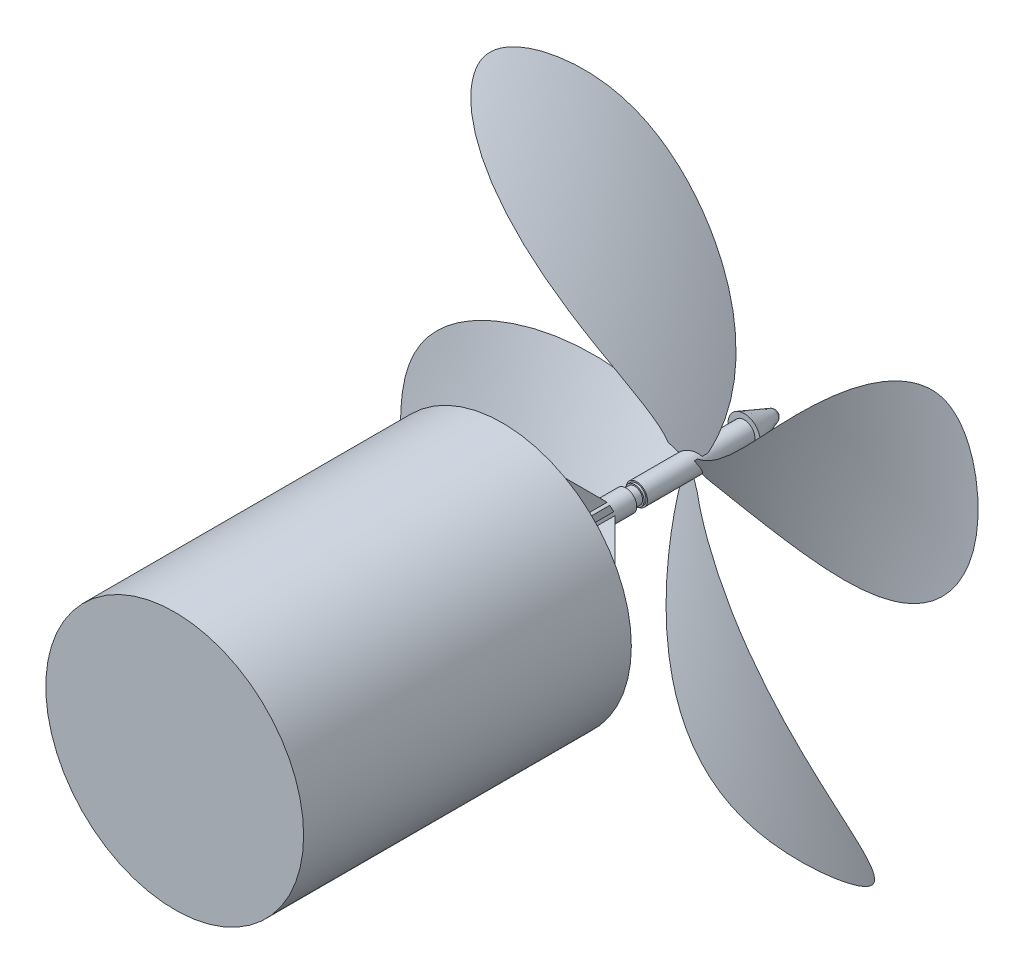
SolidWorks part; units mm, degrees
material "Gray Cast Iron"
ref_plane "Front Plane" through (0, 0, 0) normal (0, 0, 1) x (1, 0, 0)
ref_plane "Top Plane" through (0, 0, 0) normal (0, 1, 0) x (1, 0, 0)
ref_plane "Right Plane" through (0, 0, 0) normal (1, 0, 0) x (0, 0, -1)
sketch "Sketch1" plane through (0, 0, 0) normal (0, 0, 1) x (1, 0, 0)
  circle A0 centre (0, 0) radius 12
  dimension "D1" = 24
extrude "Boss-Extrude1" add sketch "Sketch1" along normal blind 30
sketch "Sketch3" plane through (0, 0, 0) normal (0, 0, 1) x (1, 0, 0)
  circle A0 centre (0, 0) radius 1
  dimension "D1" = 2
extrude "Boss-Extrude2" add sketch "Sketch3" against normal blind 15
sketch "Sketch4" plane through (0, 0, 0) normal (0, 0, 1) x (1, 0, 0)
  line L0 (0.5, 0) -> (0, 0) construction
  line L1 (0, 1) -> (0, -1) construction
  line L2 (0.5, 0) -> (0.5, 0.866) construction
  line L3 (0.25, 0) -> (0.25, 0.9682) construction
  line L4 (0.25, 0.9682) -> (0.25, 10.9682)
  line L5 (-0.25, 0.9682) -> (-0.25, 10.9682)
  line L6 (0.25, 10.9682) -> (-0.25, 10.9682)
  circle A0 centre (0, 0) radius 1 construction
  circle A1 centre (0, 0) radius 1 construction
  arc A2 (-0.25, 0.9682) -> (0.25, 0.9682) centre (0, 0) cw
  dimension "D1" = 10
extrude "Boss-Extrude3" add sketch "Sketch4" against normal blind 10 contours L5 A2 L4 L6
chamfer "Chamfer1" distance 10 angle 45 1 edges at (0, 10.9682, -10)
pattern_circular "CirPattern1" count 8 every 45 about axis through (0, 0, 0) along (0, 0, 1) of "Boss-Extrude3", "Chamfer1"
sketch "Sketch5" plane through (0, 0, 0) normal (0, 0, 1) x (1, 0, 0)
  circle A0 centre (0, 0) radius 12
  circle A1 centre (0, 0) radius 10.9682
extrude "Boss-Extrude4" add sketch "Sketch5" against normal blind 0.5
ref_plane "Plane1" through (0, 0, -12) normal (0, 0, 1) x (1, 0, 0)
sketch "Sketch6" plane through (0, 0, -12) normal (0, 0, 1) x (1, 0, 0)
  circle A0 centre (0, 0) radius 1
  circle A1 centre (0, 0) radius 0.75
  dimension "D1" = 1.5
extrude "Cut-Extrude1" cut sketch "Sketch6" against normal through all
ref_plane "Plane2" through (0, 0, -13) normal (0, 0, 1) x (1, 0, 0)
sketch "Sketch7" plane through (0, 0, -13) normal (0, 0, 1) x (1, 0, 0)
  line L0 (-0.75, 0) -> (-1, 0) construction
  circle A0 centre (0, 0) radius 0.75 construction
  arc A1 (-0.9682, 0.25) -> (-0.9682, -0.25) centre (0, 0) ccw construction
  circle A2 centre (0, 0) radius 0.875
  circle A3 centre (0, 0) radius 1 construction
  point P10 (0.875, 0)
  dimension "D1" = 0.125
extrude "Boss-Extrude5" add sketch "Sketch7" along normal blind 0.2
ref_plane "Plane3" through (0, 0, -15) normal (0, 0, 1) x (1, 0, 0)
sketch "Sketch8" plane through (0, 0, -15) normal (0, 0, 1) x (1, 0, 0)
  circle A0 centre (0, 0) radius 0.75
extrude "Boss-Extrude6" add sketch "Sketch8" against normal blind 8
ref_plane "Plane4" through (0, 0, -23) normal (0, 0, -1) x (-1, 0, 0)
sketch "Sketch9" plane through (0, 0, -23) normal (0, 0, -1) x (-1, 0, 0)
  circle A0 centre (0, 0) radius 1.5
  dimension "D1" = 3
sketch "Sketch10" plane through (0, 0, -23) normal (0, 0, -1) x (-1, 0, 0)
  circle A0 centre (0, 0) radius 1
  dimension "D1" = 2
ref_plane "Plane5" through (0, 28, 0) normal (0, 1, 0) x (1, 0, 0)
extrude "Boss-Extrude9" add sketch "Sketch10" against normal blind 10
extrude "Boss-Extrude10" add sketch "Sketch9" along normal blind 3 draft 20
fillet "Fillet2" radius 0.5 1 edges at (-0.4081, 0, -26)
sketch "Sketch13" plane through (0, 0, 0) normal (1, 0, 0) x (0, 0, -1)
  line L0 (13, 0) -> (23, 0) construction
  line L1 (13, 1) -> (13, -1) construction
  line L2 (23, 1.5) -> (23, -1.5) construction
  line L3 (23, -13.2) -> (23, 13.2) construction
  line L4 (13, -30) -> (23, -30)
  line L5 (13, -30) -> (13, 30)
  line L6 (13, 30) -> (23, 30)
  line L7 (23, -30) -> (23, 30)
  line L8 (13, -30) -> (23, 30) construction
  line L9 (13, 30) -> (23, -30) construction
  line L10 (18, 30) -> (18, -30)
  point P6 (18, 0)
  dimension "D1" = 60
  dimension "D2" = 10
ref_plane "Plane6" through (28, 0, 0) normal (1, 0, 0) x (0, 0, -1)
sketch "Sketch14" plane through (28, 0, 0) normal (1, 0, 0) x (0, 0, -1)
  line L0 (13, 30) -> (23, -30)
surface "Surface-Loft2"
other "Flex1" parameters "D0"=65, "D1"=0, "D2"=0
sketch "Sketch15" plane through (0, 0, -23) normal (0, 0, -1) x (-1, 0, 0)
  line L0 (-7.5769, 7.9305) -> (-0.5079, 0.8614) construction
  circle A0 centre (0, 0) radius 1.5 construction
  spline S0 degree 3 poles (-1.0581, -1.0633) (-9.8445, -5.0895) (-29.9183, -3.6373) (-26.1769, 17.6953) (-17.6752, 20.3586) (-6.0739, 2.3848) (-0.869, 1.2226) knots 0 0 0 0 0.425747 0.573054 0.613539 1 1 1 1
  spline S1 degree 3 poles (-26.5858, -30.8197) (-26.3562, -30.4792) (-25.895, -29.7954) (-25.1991, -28.7674) (-24.4909, -27.7335) (-23.5331, -26.3588) (-22.3046, -24.6506) (-20.8387, -22.7098) (-19.2461, -20.695) (-17.5366, -18.6283) (-15.7653, -16.5706) (-14.2241, -14.8301) (-12.5418, -12.9683) (-10.749, -11.0263) (-8.7794, -8.9419) (-7.0965, -7.1928) (-5.3435, -5.3926) (-3.7251, -3.7503) (-2.2688, -2.2816) (-1.2604, -1.267) (-0.5365, -0.5382) (-0.1481, -0.1486) (0, 0) knots 0 0 0 0 0.03086 0.061979 0.09334 0.124925 0.187393 0.249874 0.304039 0.374876 0.444209 0.499863 0.542255 0.624853 0.690304 0.749895 0.801762 0.874958 0.921196 0.957505 0.983792 1 1 1 1 construction
  point P2 (0, 0)
  point P4 (-22.1981, 18.936)
  point P6 (-14.3388, -6.3258)
  point P8 (-27.1802, 4.3403)
  point P10 (-22.584, 19.8483)
  point P11 (-11.532, 9.3225)
  point P18 (-26.2329, 0.6914)
  point P19 (-11.3565, 8.1647)
  point P20 (-22.9349, 21.0412)
  point P21 (-7.8129, 5.5332)
  point P22 (-14.0581, -4.6417)
  point P23 (-25.8821, 0.6914)
  point P24 (-23.8229, 19.0847)
  point P25 (-13.5064, 12.1514)
  point P26 (-26.663, 7.2646)
  point P27 (-24.2823, 20.9642)
  point P28 (-9.9563, 8.81)
  point P29 (-22.3193, 0)
  point P30 (-23.8493, 18.351)
curve "Curve1"
surface "Surface-Trim1"
pattern_circular "CirPattern2" count 4 over 360 about axis through (0, 0, -13) along (0, 0, -1) reverse direction yes of bodies 116
